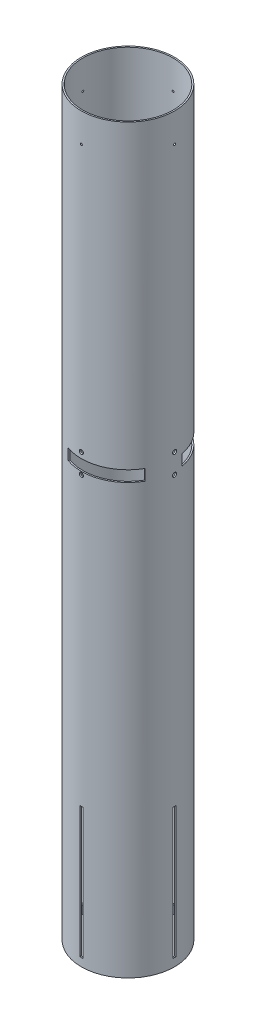
SolidWorks part; units mm, degrees
material "A-Glass Fiber"
ref_plane "Front Plane" through (0, 0, 0) normal (0, 0, 1) x (1, 0, 0)
ref_plane "Top Plane" through (0, 0, 0) normal (0, 1, 0) x (1, 0, 0)
ref_plane "Right Plane" through (0, 0, 0) normal (1, 0, 0) x (0, 0, -1)
sketch "Sketch1" plane through (0, 0, 0) normal (0, 1, 0) x (1, 0, 0)
  circle A0 centre (0, 0) radius 49.53
  circle A1 centre (0, 0) radius 51.1048
  dimension "D1" = 99.06
  dimension "D2" = 102.2096
extrude "Boss-Extrude1" add sketch "Sketch1" along normal blind 812.8
ref_plane "Plane1" through (0, 0, 0) normal (0.7071, 0, 0.7071) x (0.7071, 0, -0.7071)
ref_axis "Axis1" through (0, 812.8, 0) along (0, -1, 0)
sketch "Sketch2" plane through (0, 0, 0) normal (1, 0, 0) x (0, 0, -1)
  line L0 (0, 0) -> (0, 8.89)
  line L1 (1.5875, 8.89) -> (-1.5875, 8.89)
  line L2 (1.5875, 8.89) -> (1.5875, 152.4)
  line L3 (1.5875, 152.4) -> (-1.5875, 152.4)
  line L4 (-1.5875, 8.89) -> (-1.5875, 152.4)
  line L5 (1.5875, 8.89) -> (-1.5875, 152.4) construction
  line L6 (1.5875, 152.4) -> (-1.5875, 8.89) construction
  line L7 (51.1048, 812.8) -> (-51.1048, 812.8) construction
  line L8 (51.1048, 812.8) -> (-51.1048, 812.8)
  line L9 (0, 812.8) -> (0, 488.95)
  line L10 (-51.1048, 0) -> (51.1048, 0) construction
  circle A0 centre (0, 488.95) radius 2.25
  point P0 (0, 80.645)
  dimension "D4" = 4.5
  dimension "D1" = 3.175
  dimension "D5" = 488.95
  dimension "D3" = 152.4
  dimension "D2" = 8.89
extrude "Cut-Extrude1" cut sketch "Sketch2" against normal through all contours L4 L1 L2 L3 region at (0, 80.645, 0)
pattern_circular "CirPattern1" count 4 over 360 about axis through (0, 0, 0) along (0, 1, 0) of "Cut-Extrude1" reverse direction yes
extrude "Cut-Extrude2" cut sketch "Sketch2<3>" against normal through all contours A0 region at (0, 487.404, 1.546)
sketch "Sketch2<3>" plane through (0, 0, 0) normal (1, 0, 0) x (0, 0, -1) same geometry as "Sketch2"
pattern_circular "CirPattern2" count 4 over 360 about axis through (0, 812.8, 0) along (0, -1, 0) of "Cut-Extrude2"
sketch "Sketch3" plane through (0, 0, 0) normal (0.7071, 0, 0.7071) x (0.7071, 0, -0.7071)
  line L0 (0, 0) -> (0, 127) construction
  circle A0 centre (0, 127) radius 3.175
  dimension "D1" = 6.35
  dimension "D2" = 127
extrude "Cut-Extrude3" cut sketch "Sketch3" against normal through all
sketch "Sketch7" plane through (0, 0, 0) normal (0, 1, 0) x (1, 0, 0)
  line L0 (0, 0) -> (-44.2581, -25.5524)
  line L1 (0, 0) -> (0, 93.232) construction
  line L2 (0, 0) -> (-32.8495, 39.1485)
  line L3 (-51.1048, 0) -> (0, 0) construction
  arc A0 (-51.0552, 2.25) -> (-51.0552, -2.25) centre (0, 0) ccw construction
  circle A1 centre (0, 0) radius 49.53 construction
  circle A2 centre (0, 0) radius 51.1048
  circle A3 centre (0, 0) radius 51.1048
  circle A4 centre (0, 0) radius 49.53
  circle A5 centre (0, 0) radius 51.1048 construction
  arc A6 (2.25, 51.0552) -> (-2.25, 51.0552) centre (0, 0) ccw construction
  arc A7 (-51.0552, 2.25) -> (-51.0552, -2.25) centre (0, 0) ccw
  arc A8 (2.25, 51.0552) -> (-2.25, 51.0552) centre (0, 0) ccw
  dimension "D1" = 80
  dimension "D3" = 30
  dimension "D2" = 0
extrude "Cut-Extrude4" cut sketch "Sketch7" against normal blind 12.065 from offset 482.6 contours A4 A3 L0 region at (-43.9137, 0, 24.5741)
pattern_circular "CirPattern3" count 3 over 360 about axis through (0, 812.8, 0) along (0, -1, 0) of "Cut-Extrude4"
pattern_linear "LPattern1" count 2 spacing 21.6916 along (0, -1, 0) of "CirPattern2"
sketch "Sketch8" plane through (0, 0, 0) normal (0, 0, 1) x (1, 0, 0)
  line L0 (49.53, 812.8) -> (-49.53, 812.8) construction
  circle A0 centre (0, 781.05) radius 1.0922
  dimension "D1" = 2.1844
  dimension "D2" = 31.75
extrude "Cut-Extrude5" cut sketch "Sketch8" against normal through all
pattern_circular "CirPattern4" count 4 over 360 about axis through (0, 812.8, 0) along (0, -1, 0) of "Cut-Extrude5"
sketch "Sketch9" plane through (0, 0, 0) normal (0, 0, 1) x (1, 0, 0)
  line L0 (51.1048, 812.8) -> (-51.1048, 812.8) construction
  point P0 (0, 752.856)
  dimension "D1" = 59.944
hole_wizard "1/2 Clearance Hole4" positions "Sketch17" profile "Sketch18" hole size "1/2" standard "ANSI Inch" end condition through all
sketch "Sketch17" plane through (0, 0, 0) normal (0, 0, 1) x (1, 0, 0)
  point P0 (0, 752.856)
sketch "Sketch18" plane through (0, 752.856, 0) normal (1, 0, 0) x (0, -1, 0)
  line L0 (0, 0) -> (0, 51.1048)
  line L1 (0, 51.1048) -> (6.5481, 51.1048)
  line L2 (6.5481, 51.1048) -> (6.5481, 0)
  line L5 (6.5481, 0) -> (0, 0)
  line L11 (0, -6.35) -> (0, 107.95) construction
  dimension "Thru Hole Dia." = 13.0962
  dimension "Thru Hole Depth" = 51.1048
ref_plane "Plane3" through (24.3888, 0, -29.0654) normal (0.6428, 0, -0.766) x (-0.766, 0, -0.6428)
equation "\"D1@Boss-Extrude1\" = \"Aft_Section_Length\""
equation "\"AB_Coupler_OD_Length\"= 1in"
equation "\"AB_Coupling_Section_Length\"= 0.375in"
equation "\"AB_Coupler_Length\"= \"AB_Coupler_OD_Length\" + \"AB_Coupling_Section_Length\" * 2"
equation "\"AB_Coupler_Num_Screws\"= 4"
equation "\"AB_Coupling_Screw_Diameter\"= 4.5mm"
equation "\"Aft_Section_Length\" = 32in"
equation "\"D4@Sketch2\"=\"AB_Coupling_Screw_Diameter\""
equation "\"D1@CirPattern2\"=\"AB_Coupler_Num_Screws\""
equation "\"Rail_Nut_From_Bottom\"= 5in"
equation "\"Rail_Nut_Diam\"= 0.25in"
equation "\"D1@Sketch3\"=\"Rail_Nut_Diam\""
equation "\"D2@Sketch3\"=\"Rail_Nut_From_Bottom\""
equation "\"AB_BKHD_Thickness\"= 0.375in"
equation "\"AB_Mount_From_Bottom\"= 19.25in"
equation "\"Cutout_Angle\" = 60"
equation "\"Motor_OD\" = 54.4mm"
equation "\"Motor_Length\" = 401mm"
equation "\"Mid_Coupler_Length\" = 12in"
equation "\"AB_Paddle_Height\" = 0.375in"
equation "\"Num_Cutouts\" = 4"
equation "\"AB_Coupler_OD\"= 4.024in"
equation "\"AB_Coupler_ID\"= 3.7in"
equation "\"AB_Coupler_Surface_Diameter\"= 3.899in"
equation "\"AB_Central_Bushing_Length\" = 0.75in"
equation "\"Lead_Screw_Dist\" = 2in"
equation "\"Lead_Screw_Diam\" = 0.375in"
equation "\"Lead_Screw_Length\" = \"Mid_Coupler_Length\" + 2*0.375in + 2*0.5in"
equation "\"Paddle_Pin_Offset\" = 0.25in"
equation "\"Paddle_Pin_Radius\" = 2.25*2/3in"
equation "\"Paddle_Gear_OD\" = 3.2in"
equation "\"Fwd_BKHD_From_Top\" = 18in"
equation "\"Body_Tube_OD\"= 4.024in"
equation "\"Body_Tube_ID\"= 3.90in"
equation "\"Coupler_OD\" = 3.899in"
equation "\"Coupler_ID\" = 3.755in"
equation "\"Fwd_Section_Length\" = 20in"
equation "\"Mid_Section_Length\" = 4in"
equation "\"Aft_Upper_Tube_Length\" = 10in"
equation "\"Aft_Lower_Tube_Length\" = 18in"
equation "\"Nosecone_Coupler_Length\" = 5in"
equation "\"Avionics_Bulkhead_Thickness\" = 0.25in"
equation "\"Avionics_Bulkhead_Lip\" = 0.125in"
equation "\"Avionics_Board_Length\" = \"Mid_Coupler_Length\" - 2*\"Avionics_Bulkhead_Lip\""
equation "\"Lead_Screw_Hole_Diam\" = 0.386in"
equation "\"Centering_Ring_Cutout_Dia\"= 1in"
equation "\"D2@Sketch1\"=\"Body_Tube_OD\""
equation "\"D1@Sketch1\"=\"Body_Tube_ID\""
equation "\"D5@Sketch2\"=\"AB_Mount_From_Bottom\""
equation "\"D19@Cut-Extrude4\"=\"AB_Mount_From_Bottom\"-0.25"
